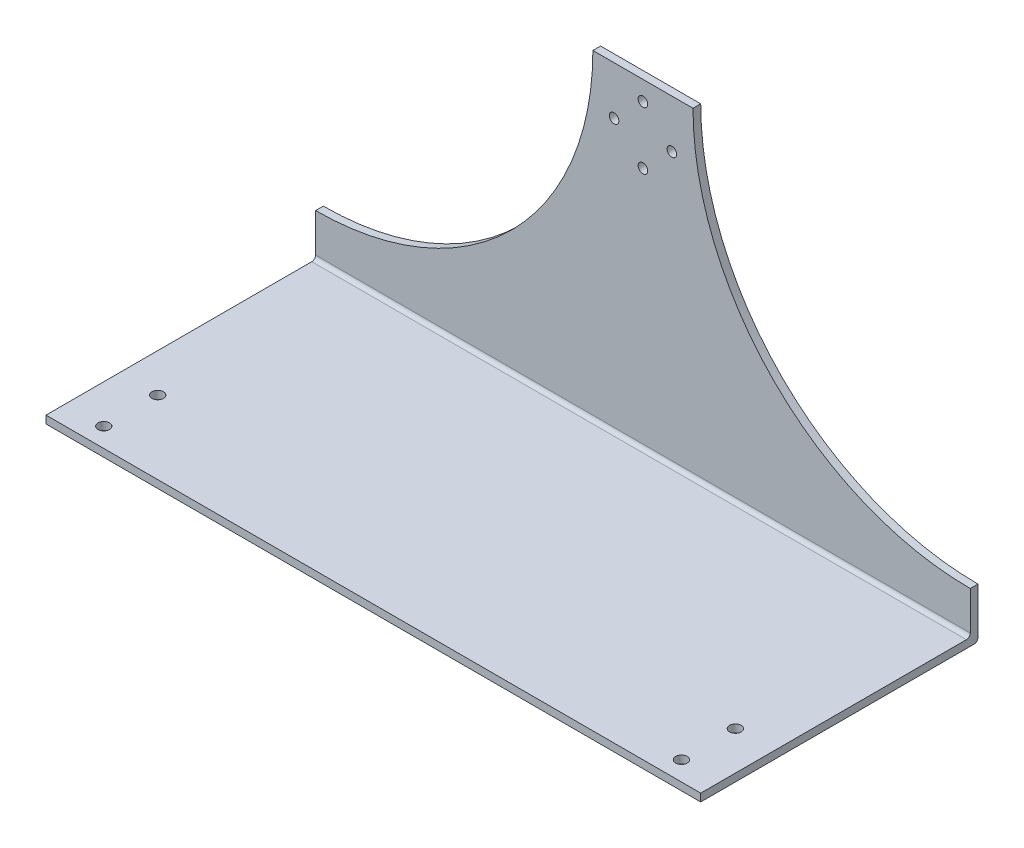
SolidWorks part; units mm, degrees
ref_plane "Front Plane" through (0, 0, 0) normal (0, 0, 1) x (1, 0, 0)
ref_plane "Top Plane" through (0, 0, 0) normal (0, 1, 0) x (1, 0, 0)
ref_plane "Right Plane" through (0, 0, 0) normal (1, 0, 0) x (0, 0, -1)
sketch "Sketch1" plane through (0, 0, 0) normal (0, 1, 0) x (1, 0, 0)
  line L1 (-85.5577, -1.2168) -> (84.4423, -1.2168)
  line L2 (-85.5577, -1.2168) -> (-85.5577, -71.2168)
  line L3 (-85.5577, -71.2168) -> (84.4423, -71.2168)
  line L4 (84.4423, -1.2168) -> (84.4423, -71.2168)
  dimension "D1" = 170
  dimension "D2" = 70
extrude "Boss-Extrude1" add sketch "Sketch1" along normal blind 2
sketch "Sketch2" plane through (0, 2, 0) normal (0, 1, 0) x (1, 0, 0)
  line L0 (-85.5577, -71.2168) -> (84.4423, -71.2168) construction
  line L1 (-85.5577, -1.2168) -> (-85.5577, -71.2168) construction
  circle A0 centre (-75.5577, -52.2168) radius 1.5
  circle A1 centre (-75.5577, -66.2168) radius 1.5
  circle A2 centre (74.4423, -52.2168) radius 1.5
  circle A3 centre (74.4423, -66.2168) radius 1.5
  dimension "D1" = 150
  dimension "D2" = 150
  dimension "D3" = 14
  dimension "D4" = 5
  dimension "D5" = 10
extrude "Cut-Extrude1" cut sketch "Sketch2" against normal blind 22 and the other way blind 22
sketch "Sketch4" plane through (0, 0, 1.2168) normal (0, 0, -1) x (-1, 0, 0)
  line L1 (-84.4423, 0) -> (85.5577, 0)
  line L2 (-84.4423, 0) -> (-84.4423, 85)
  line L3 (-84.4423, 85) -> (85.5577, 85)
  line L4 (85.5577, 0) -> (85.5577, 85)
  dimension "D1" = 170
  dimension "D2" = 85
extrude "Boss-Extrude2" add sketch "Sketch4" along normal blind 2
fillet "Fillet2" radius 1 1 edges at (-0.5577, 0, -0.7832)
fillet "Fillet3" radius 1 1 edges
sketch "Sketch5" plane through (0, 0, 1.2168) normal (0, 0, 1) x (1, 0, 0)
  circle A0 centre (-85.5577, 85) radius 72
  circle A1 centre (84.4423, 85) radius 72
  point P6 (0, 0)
sketch "Sketch6" plane through (0, 0, 1.2168) normal (0, 0, 1) x (1, 0, 0)
  line L0 (-85.5577, 85) -> (84.4423, 85) construction
  line L1 (-85.5577, 3) -> (-85.5577, 85) construction
  line L2 (84.4423, 85) -> (84.4423, 3) construction
  circle A0 centre (-0.5577, 80) radius 1.25
  circle A1 centre (-0.5577, 65) radius 1.25
  circle A2 centre (6.9423, 72.5) radius 1.25
  circle A3 centre (-8.0577, 72.5) radius 1.25
  dimension "D1" = 15
  dimension "D2" = 5
  dimension "D3" = 15
  dimension "D4" = 77.5
  dimension "D5" = 85
  dimension "D6" = 7.5
extrude "Cut-Extrude3" cut sketch "Sketch6" against normal blind 12 and the other way blind 12
extrude "Cut-Extrude4" cut sketch "Sketch5" against normal blind 12 and the other way blind 12 contours A1 | A0
